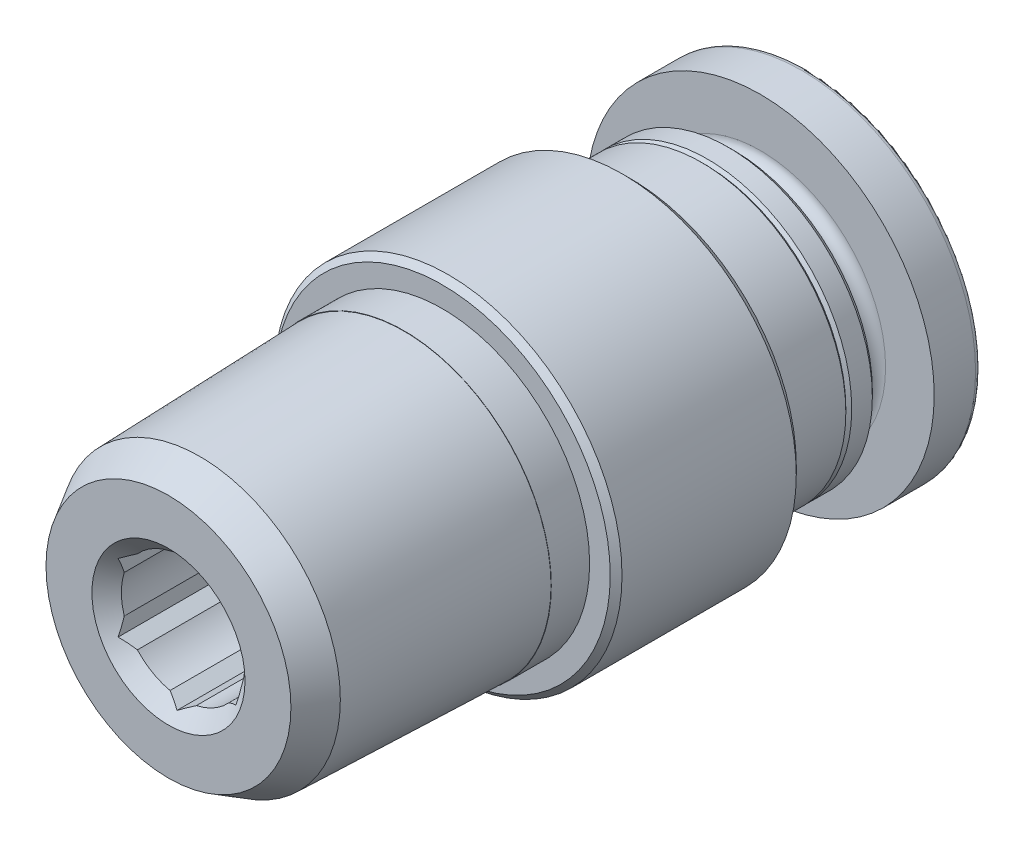
SolidWorks part; units mm, degrees
ref_plane "Front Plane" through (0, 0, 0) normal (0, 0, 1) x (1, 0, 0)
ref_plane "Top Plane" through (0, 0, 0) normal (0, 1, 0) x (1, 0, 0)
ref_plane "Right Plane" through (0, 0, 0) normal (1, 0, 0) x (0, 0, -1)
ref_plane "Plane1" through (0, 0, 0) normal (1, 0, 0) x (0, 0, -1)
sketch "Sketch1" plane through (0, 0, 0) normal (1, 0, 0) x (0, 0, -1)
  line L0 (0, 0) -> (0, 5.9)
  line L1 (0, 5.9) -> (7.4172, 5.9)
  line L2 (7.4172, 5.9) -> (7.7, 5.6172)
  line L3 (7.7, 5.6172) -> (7.7, 4.9)
  line L4 (7.7, 4.9) -> (10.1, 4.9)
  line L5 (10.1, 4.9) -> (10.2, 4.8)
  line L6 (10.2, 4.8) -> (10.3, 4.9)
  line L7 (10.3, 4.9) -> (11, 4.9)
  line L8 (11, 4.9) -> (11.2, 4.7)
  line L9 (11.2, 4.7) -> (11.2, 3.875)
  line L10 (11.2, 3.875) -> (11.725, 3.875)
  line L11 (12.1, 4.25) -> (12.1, 5.9)
  line L12 (12.1, 5.9) -> (13.5046, 5.9)
  line L13 (13.7015, 5.7347) -> (14.1, 3.475)
  line L14 (14.1, 3.475) -> (14.1, 0)
  line L15 (14.1, 0) -> (0, 0)
  line L16 (14.1, 0) -> (0, 0) construction
  arc A0 (11.725, 3.875) -> (12.1, 4.25) centre (11.725, 4.25) ccw
  arc A1 (13.5046, 5.9) -> (13.7015, 5.7347) centre (13.5046, 5.7) cw
revolve "Revolve1" add sketch "Sketch1" angle 360 about L16 reverse direction yes
ref_plane "Plane2" through (0, 0, 0) normal (1, 0, 0) x (0, 0, -1)
sketch "Sketch2" plane through (0, 0, 0) normal (1, 0, 0) x (0, 0, -1)
  line L0 (-8, 0) -> (-8, 4.1581)
  line L1 (-8, 4.1581) -> (-6.9362, 4.7723)
  line L2 (-6.9362, 4.7723) -> (0, 4.9889)
  line L3 (0, 4.9889) -> (0, 0)
  line L4 (0, 0) -> (-8, 0)
  line L5 (0, 0) -> (-8, 0) construction
revolve "Revolve2" add sketch "Sketch2" angle 360 about L5 reverse direction yes
ref_plane "Plane3" through (0, 0, 0) normal (1, 0, 0) x (0, 0, -1)
sketch "Sketch3" plane through (0, 0, 0) normal (1, 0, 0) x (0, 0, -1)
  line L0 (0, 5.9) -> (0, 5)
  line L1 (0, 5) -> (1.3, 5)
  line L2 (1.3, 5) -> (1.3, 5.7)
  line L3 (1.3, 5.7) -> (1.5, 5.9)
  line L4 (1.5, 5.9) -> (0, 5.9)
  line L5 (50, 0) -> (-50, 0) construction
revolve "Cut-Revolve1" cut sketch "Sketch3" angle 360 about L5 reverse direction yes
ref_plane "Plane4" through (0, 0, 0) normal (1, 0, 0) x (0, 0, -1)
sketch "Sketch4" plane through (0, 0, 0) normal (1, 0, 0) x (0, 0, -1)
  line L0 (-8, 0) -> (-8, 2.6)
  line L1 (-8, 2.6) -> (-7.5, 2.1)
  line L2 (-7.5, 2.1) -> (-2.9, 2.1)
  line L3 (-2.9, 2.1) -> (-2.9, 3.175)
  line L4 (-2.9, 3.175) -> (13.8, 3.175)
  line L5 (14.1, 3.475) -> (14.1, 0)
  line L6 (14.1, 0) -> (-8, 0)
  line L7 (14.1, 0) -> (-8, 0) construction
  arc A0 (13.8, 3.175) -> (14.1, 3.475) centre (13.8, 3.475) ccw
revolve "Cut-Revolve2" cut sketch "Sketch4" angle 360 about L7 reverse direction yes
ref_plane "Plane5" through (0, 0, 2.9) normal (0, 0, 1) x (1, 0, 0)
sketch "Sketch5" plane through (0, 0, 2.9) normal (0, 0, 1) x (1, 0, 0)
  line L0 (-2, -1.1547) -> (0, -2.3094)
  line L1 (0, -2.3094) -> (2, -1.1547)
  line L2 (2, -1.1547) -> (2, 1.1547)
  line L3 (2, 1.1547) -> (0, 2.3094)
  line L4 (0, 2.3094) -> (-2, 1.1547)
  line L5 (-2, 1.1547) -> (-2, -1.1547)
extrude "Cut-Extrude1" cut sketch "Sketch5" along normal blind 5.1
